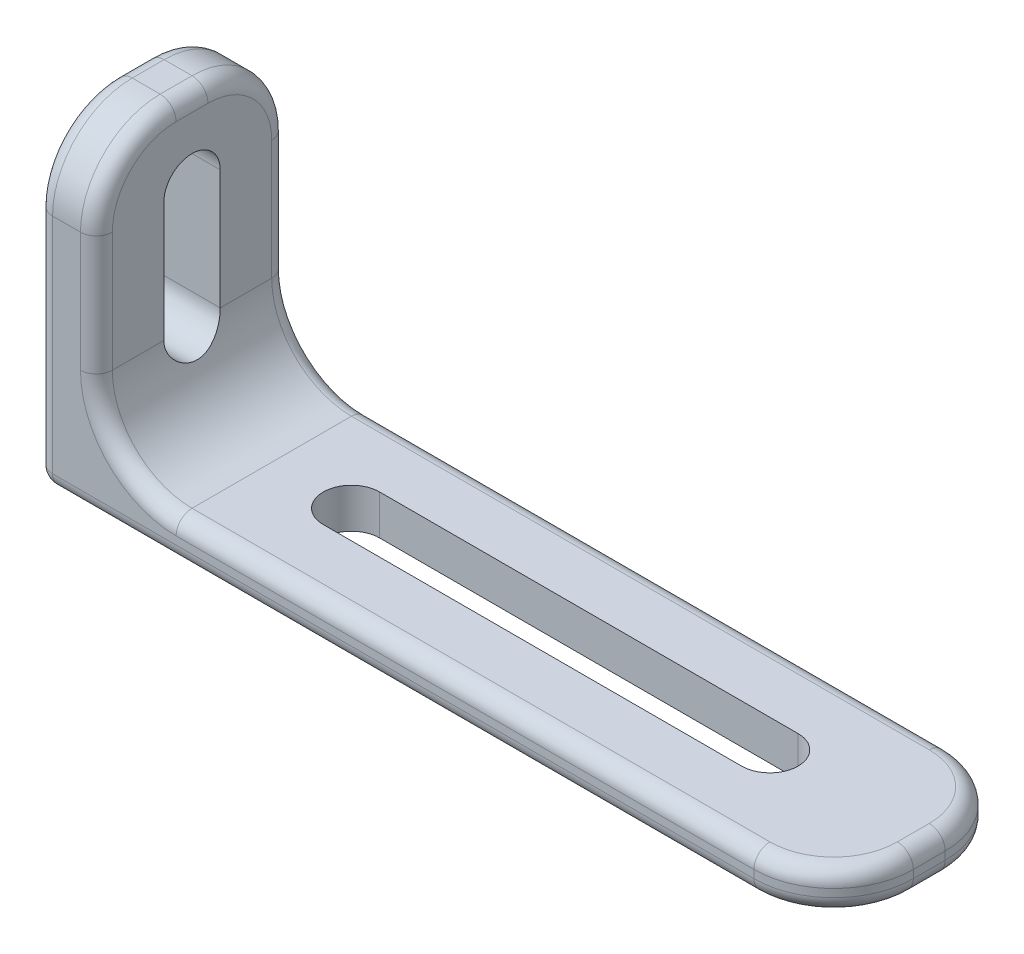
SolidWorks part; units mm, degrees
ref_plane "Plan de face" through (0, 0, 0) normal (0, 0, 1) x (1, 0, 0)
ref_plane "Plan de dessus" through (0, 0, 0) normal (0, 1, 0) x (1, 0, 0)
ref_plane "Plan de droite" through (0, 0, 0) normal (1, 0, 0) x (0, 0, -1)
sketch "Esquisse1" plane through (0, 0, 0) normal (0, 1, 0) x (1, 0, 0)
  line L0 (-26.9875, 7.62) -> (-26.9875, -7.62)
  line L1 (-31.75, -7.62) -> (31.75, -7.62)
  line L2 (-31.75, -7.62) -> (-31.75, 7.62)
  line L3 (-31.75, 7.62) -> (31.75, 7.62)
  line L4 (31.75, -7.62) -> (31.75, 7.62)
  line L5 (-31.75, -7.62) -> (31.75, 7.62) construction
  line L6 (-31.75, 7.62) -> (31.75, -7.62) construction
  line L7 (19.05, 0) -> (-14.2875, 0) construction
  line L8 (19.05, -2.2479) -> (-14.2875, -2.2479)
  line L9 (19.05, 2.2479) -> (-14.2875, 2.2479)
  arc A0 (19.05, -2.2479) -> (19.05, 2.2479) centre (19.05, 0) ccw
  arc A1 (-14.2875, 2.2479) -> (-14.2875, -2.2479) centre (-14.2875, 0) ccw
  point P0 (0, 0)
  point P10 (2.3813, 0)
  dimension "D6" = 4.4958
  dimension "D1" = 63.5
  dimension "D2" = 15.24
  dimension "D3" = 4.7625
  dimension "D4" = 12.7
  dimension "D5" = 12.7
extrude "Boss.-Extru.1" add sketch "Esquisse1" along normal blind 3.175 contours L1 L4 L3 L0 A1 L9 A0 L8 region at (2.3813, 0, -7.0132)
extrude "Boss.-Extru.2" add sketch "Esquisse1<3>" along normal blind 25.4 contours L3 L2 L1 L0 region at (-29.3687, 0, 0)
sketch "Esquisse1<3>" plane through (0, 0, 0) normal (0, 1, 0) x (1, 0, 0) same geometry as "Esquisse1"
sketch "Esquisse3" plane through (-31.75, 0, 0) normal (-1, 0, 0) x (0, 0, 1)
  line L0 (0, 19.05) -> (0, 9.525) construction
  line L1 (2.2479, 19.05) -> (2.2479, 9.525)
  line L2 (-2.2479, 19.05) -> (-2.2479, 9.525)
  line L3 (7.62, 25.4) -> (-7.62, 25.4) construction
  line L5 (-7.62, 3.175) -> (7.62, 3.175) construction
  arc A0 (2.2479, 19.05) -> (-2.2479, 19.05) centre (0, 19.05) ccw
  arc A1 (-2.2479, 9.525) -> (2.2479, 9.525) centre (0, 9.525) ccw
  point P3 (0, 14.2875)
  dimension "D1" = 4.4958
  dimension "D2" = 6.35
  dimension "D3" = 6.35
extrude "Enlèv. mat.-Extru.1" cut sketch "Esquisse3" against normal through all both and the other way through all
fillet "Congé1" radius 6.35 5 edges at (-26.9875, 3.175, 0) (31.75, 1.5875, 7.62) (31.75, 1.5875, -7.62) (-29.3687, 25.4, -7.62) (-29.3687, 25.4, 7.62)
fillet "Congé2" radius 1.27 23 edges at (-26.9875, 25.4, 0) (-26.9875, 23.5401, -5.7601) (-26.9875, 14.2875, -7.62) (-25.1276, 5.0349, -7.62) (2.3813, 3.175, -7.62) (29.8901, 3.175, -5.7601) (31.75, 3.175, 0) (29.8901, 3.175, 5.7601) (2.3813, 3.175, 7.62) (-25.1276, 5.0349, 7.62) (-26.9875, 14.2875, 7.62) (-31.75, 9.525, -7.62) (-31.75, 23.5401, -5.7601) (-31.75, 25.4, 0) (-31.75, 23.5401, 5.7601) (-3.175, 0, -7.62) (29.8901, 0, -5.7601) (31.75, 0, 0) (29.8901, 0, 5.7601) (-26.9875, 23.5401, 5.7601) (-31.75, 9.525, 7.62) (-3.175, 0, 7.62) (-31.75, 0, 0)
